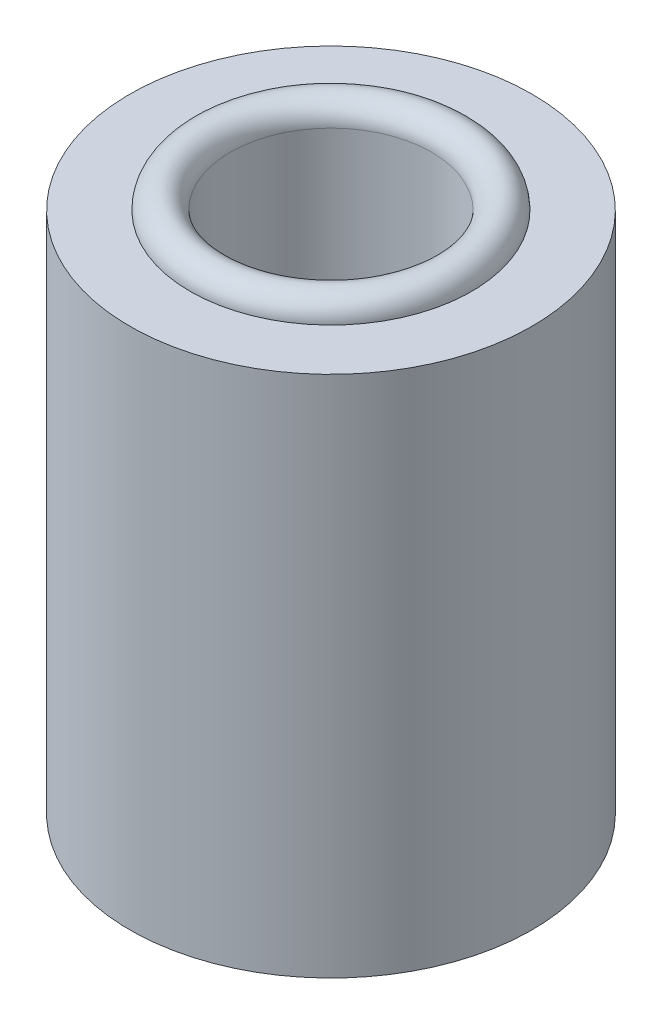
SolidWorks part; units mm, degrees
ref_plane "Front Plane" through (0, 0, 0) normal (0, 0, 1) x (1, 0, 0)
ref_plane "Top Plane" through (0, 0, 0) normal (0, 1, 0) x (1, 0, 0)
ref_plane "Right Plane" through (0, 0, 0) normal (1, 0, 0) x (0, 0, -1)
sketch "Profile Sketch" plane through (0, 0, 0) normal (0, 1, 0) x (1, 0, 0)
  circle A0 centre (0, 0) radius 10
  circle A1 centre (0, 0) radius 5
  dimension "D1" = 20
  dimension "D2" = 10
extrude "Cylinder Extrude" add sketch "Profile Sketch" along normal blind 26
sketch "Lip Ring Sketch" plane through (0, 26, 0) normal (0, 1, 0) x (1, 0, 0)
  circle A0 centre (0, 0) radius 5
  circle A1 centre (0, 0) radius 7
  circle A2 centre (0, 0) radius 5 construction
  dimension "D1" = 2
extrude "Bottom Lip Ring Extrude" add sketch "Lip Ring Sketch" along normal blind 1
fillet "Bottom Ring Fillet" 2 edges at (0, 27, 7) (0, 27, 5) type full round first side face at (0, 27, 7) second side face at (0, 0, 5) middle face at (0, 27, 7)
extrude "Top Lip Ring Extrude" add sketch "Sketch2<2>" against normal blind 1 from surface starting at face at (0, 0, 10)
sketch "Sketch2<2>" plane through (0, 26, 0) normal (0, 1, 0) x (1, 0, 0) same geometry as "Lip Ring Sketch"
fillet "Top Ring Fillet" 2 edges at (0, -1, 7) (0, -1, 5) type full round first side face at (0, -1, 7) second side face at (0, 26, 5) middle face at (0, -1, 5)
